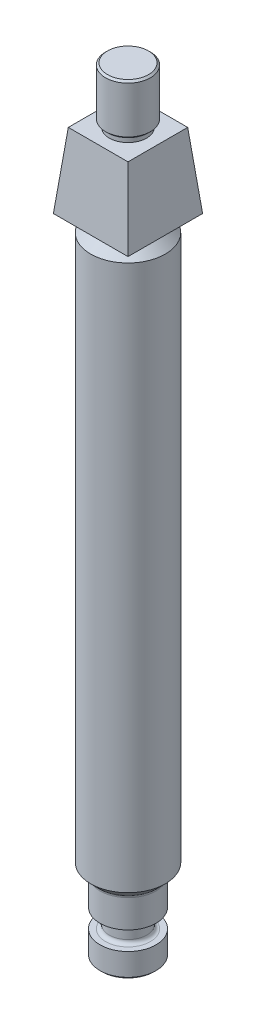
SolidWorks part; units mm, degrees
ref_plane "Front Plane" through (0, 0, 0) normal (0, 0, 1) x (1, 0, 0)
ref_plane "Top Plane" through (0, 0, 0) normal (0, 1, 0) x (1, 0, 0)
ref_plane "Right Plane" through (0, 0, 0) normal (1, 0, 0) x (0, 0, -1)
sketch "Sketch1" plane through (0, 0, 0) normal (0, 1, 0) x (1, 0, 0)
  circle A0 centre (0, 0) radius 15
  dimension "D1" = 30
extrude "Boss-Extrude1" add sketch "Sketch1" along normal blind 40
sketch "Sketch2" plane through (0, 40, 0) normal (0, 1, 0) x (1, 0, 0)
  circle A0 centre (0, 0) radius 20
  dimension "D1" = 40
extrude "Boss-Extrude2" add sketch "Sketch2" along normal blind 300
sketch "Sketch4" plane through (0, 0, 0) normal (0, 0, 1) x (1, 0, 0)
  line L0 (-15, 23) -> (-10, 23)
  line L1 (-15, 40) -> (-15, 0) construction
  line L2 (-10, 23) -> (-10, 13)
  line L3 (-10, 13) -> (-15, 13)
  line L4 (-15, 13) -> (-15, 23)
  line L5 (-15, 40) -> (15, 40) construction
  point P4 (-15, 18)
  dimension "D1" = 10
  dimension "D2" = 5
  dimension "D3" = 22
revolve "Cut-Revolve1" cut sketch "Sketch4" angle 360 about axis through (0, 40, 0) along (0, -1, 0)
sketch "Sketch3" plane through (0, 340, 0) normal (0, 1, 0) x (1, 0, 0)
  circle A0 centre (0, 0) radius 15
  dimension "D1" = 30
extrude "Boss-Extrude3" add sketch "Sketch3" along normal blind 5
sketch "Sketch5" plane through (0, 345, 0) normal (0, 1, 0) x (1, 0, 0)
  line L1 (20, -20) -> (-20, -20)
  line L2 (20, -20) -> (20, 20)
  line L3 (20, 20) -> (-20, 20)
  line L4 (-20, -20) -> (-20, 20)
  line L5 (20, -20) -> (-20, 20) construction
  line L6 (20, 20) -> (-20, -20) construction
  point P0 (0, 0)
  dimension "D1" = 40
ref_plane "Plane1" through (0, 385, 0) normal (0, 1, 0) x (1, 0, 0)
sketch "Sketch6" plane through (0, 385, 0) normal (0, 1, 0) x (1, 0, 0)
  line L0 (20, -20) -> (-20, 20) construction
  line L1 (16, -16) -> (-16, -16)
  line L2 (16, -16) -> (16, 16)
  line L3 (16, 16) -> (-16, 16)
  line L4 (-16, -16) -> (-16, 16)
  line L5 (16, -16) -> (-16, 16) construction
  line L6 (16, 16) -> (-16, -16) construction
  point P0 (0, 0)
  dimension "D1" = 32
loft "Loft1" add profiles "Sketch5", "Sketch6" connector at (-20, 345, -20) connector at (-16, 385, -16)
sketch "Sketch7" plane through (0, 385, 0) normal (0, 1, 0) x (1, 0, 0)
  circle A0 centre (0, 0) radius 10
  dimension "D1" = 20
extrude "Boss-Extrude4" add sketch "Sketch7" along normal blind 3
sketch "Sketch8" plane through (0, 388, 0) normal (0, 1, 0) x (1, 0, 0)
  circle A0 centre (0, 0) radius 12
  dimension "D1" = 24
extrude "Boss-Extrude5" add sketch "Sketch8" along normal blind 27
cosmetic thread "Cosmetic Thread1" parameters "D1"=27, "D2"=20.704
chamfer "Chamfer1" distance 1 angle 45 2 edges at (0, 388, 12) (0, 415, 12)
fillet "Fillet1" radius 2 5 edges at (0, 340, 15) (0, 345, 15) (0, 13, 10) (0, 23, 10) (0, 40, 15)
chamfer "Chamfer2" distance 1 angle 45 1 edges at (0, 0, 15)
sketch "Sketch9" plane through (0, 0, 0) normal (0, 0, 1) x (1, 0, 0)
  line L0 (-20, 336.1716) -> (-20, 340)
  line L1 (-20, 340) -> (-20, 40) construction
  line L2 (-20, 336.1716) -> (-15.5858, 340.5858)
  line L3 (-20, 340) -> (-15.5858, 340.5858)
  line L4 (20, 340) -> (-20, 340) construction
  line L5 (-20, 43.8284) -> (-20, 40)
  line L6 (-20, 43.8284) -> (-15.5858, 39.4142)
  line L7 (-15.5858, 39.4142) -> (-20, 40)
  arc A0 (-17, 340) -> (-15, 342) centre (-17, 342) ccw construction
  arc A1 (-17, 340) -> (-15, 342) centre (-17, 342) ccw construction
  arc A2 (-15, 38) -> (-17, 40) centre (-17, 38) ccw construction
  arc A3 (-15, 38) -> (-17, 40) centre (-17, 38) ccw construction
  dimension "D1" = 45
  dimension "D2" = 45
revolve "Cut-Revolve2" cut sketch "Sketch9" angle 360 about axis through (0, 340, 0) along (0, -1, 0)
